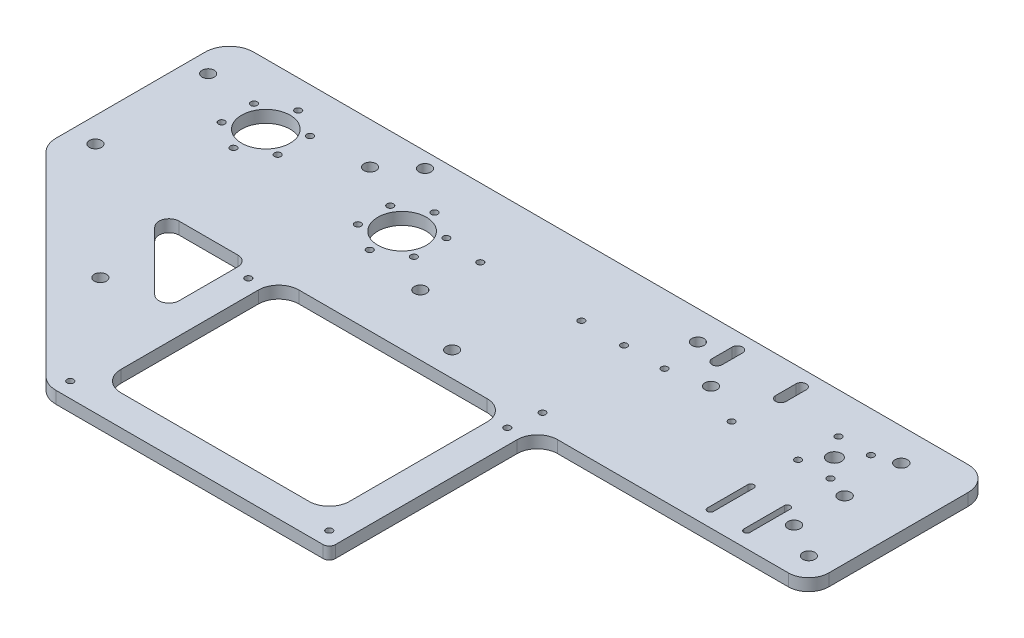
SolidWorks part; units mm, degrees
material "Policarbonato"
ref_plane "Plano frontal" through (0, 0, 0) normal (0, 0, 1) x (1, 0, 0)
ref_plane "Plano superior" through (0, 0, 0) normal (0, 1, 0) x (1, 0, 0)
ref_plane "Plano direito" through (0, 0, 0) normal (1, 0, 0) x (0, 0, -1)
sketch "Esboço1" plane through (0, 0, 0) normal (0, 1, 0) x (1, 0, 0)
  line L3 (-80.5574, -153.6487) -> (51.4721, -153.6487)
  line L4 (54.4721, -150.6487) -> (54.4721, -60.7886)
  line L6 (188.5279, -40.7886) -> (188.5279, 28)
  line L7 (176.5279, 40) -> (-176.5279, 40)
  line L8 (-188.5279, 28) -> (-188.5279, -45.6781)
  line L12 (-122.5768, -50.7886) -> (-93.5279, -50.7886)
  line L13 (-88.5279, -55.7886) -> (-88.5279, -84.8375)
  line L14 (-97.0635, -88.373) -> (-126.1124, -59.3241)
  line L15 (39.4721, -60.6487) -> (39.4721, -128.6487)
  line L16 (29.4721, -138.6487) -> (-63.5279, -138.6487)
  line L17 (-73.5279, -128.6487) -> (-73.5279, -60.6487)
  line L18 (-63.5279, -50.6487) -> (29.4721, -50.6487)
  line L20 (132.5279, 0) -> (148.5279, 0) construction
  line L21 (132.5279, 0) -> (132.5279, 20) construction
  line L22 (132.5279, 20) -> (148.5279, 20) construction
  line L23 (148.5279, 0) -> (148.5279, 20) construction
  line L24 (132.5279, 0) -> (148.5279, 20) construction
  line L25 (132.5279, 20) -> (148.5279, 0) construction
  line L30 (64.4721, -50.7886) -> (178.5279, -50.7886)
  line L31 (150.2221, -43) -> (150.2221, -23) construction
  line L32 (148.7221, -43) -> (148.7221, -23)
  line L33 (151.7221, -43) -> (151.7221, -23)
  line L34 (141.2221, -45.2211) -> (141.2221, -21.4375) construction
  line L36 (132.2221, -43) -> (132.2221, -23) construction
  line L37 (133.7221, -43) -> (133.7221, -23)
  line L38 (130.7221, -43) -> (130.7221, -23)
  line L39 (49.2221, -43) -> (150.2221, -43) construction
  line L40 (54.4721, -120.5) -> (144.9721, -120.5) construction
  line L41 (54.4721, -120.5) -> (54.4721, -7) construction
  line L42 (54.4721, -7) -> (144.9721, -7) construction
  line L43 (144.9721, -120.5) -> (144.9721, -7) construction
  line L44 (54.4721, -120.5) -> (144.9721, -7) construction
  line L45 (54.4721, -7) -> (144.9721, -120.5) construction
  line L46 (70.5279, 22) -> (70.5279, 32) construction
  line L47 (67.9779, 22) -> (67.9779, 32)
  line L48 (73.0779, 22) -> (73.0779, 32)
  line L49 (102.0279, 22) -> (102.0279, 32) construction
  line L50 (99.4779, 22) -> (99.4779, 32)
  line L51 (104.5779, 22) -> (104.5779, 32)
  line L52 (-185.0132, -54.1634) -> (-89.0426, -150.134)
  circle A0 centre (-81.0279, -58.1487) radius 1.6
  circle A1 centre (-81.0279, -146.1487) radius 1.6
  circle A2 centre (46.9721, -58.1487) radius 1.6
  circle A3 centre (46.9721, -146.1487) radius 1.6
  circle A8 centre (176.311, -38.4318) radius 3
  circle A9 centre (0, -38.4318) radius 3
  circle A11 centre (-140.5279, 10) radius 12
  circle A20 centre (-140.5279, 10) radius 16 construction
  circle A21 centre (-140.5279, -6) radius 1.6
  circle A22 centre (-154.3843, 2) radius 1.6
  circle A23 centre (-154.3843, 18) radius 1.6
  circle A24 centre (-84.3674, 32.5) radius 3
  circle A25 centre (-176.311, -38.4318) radius 3
  circle A26 centre (140.5279, 10) radius 3.5
  circle A27 centre (148.5279, 0) radius 1.6
  circle A28 centre (148.5279, 20) radius 1.6
  circle A29 centre (132.5279, 0) radius 1.6
  circle A30 centre (132.5279, 20) radius 1.6
  arc A31 (51.4721, -153.6487) -> (54.4721, -150.6487) centre (51.4721, -150.6487) ccw
  arc A34 (188.5279, 28) -> (176.5279, 40) centre (176.5279, 28) ccw
  arc A35 (-176.5279, 40) -> (-188.5279, 28) centre (-176.5279, 28) ccw
  arc A39 (-93.5279, -50.7886) -> (-88.5279, -55.7886) centre (-93.5279, -55.7886) cw
  arc A40 (-88.5279, -84.8375) -> (-97.0635, -88.373) centre (-93.5279, -84.8375) cw
  arc A41 (-126.1124, -59.3241) -> (-122.5768, -50.7886) centre (-122.5768, -55.7886) cw
  arc A42 (39.4721, -128.6487) -> (29.4721, -138.6487) centre (29.4721, -128.6487) cw
  arc A43 (-63.5279, -138.6487) -> (-73.5279, -128.6487) centre (-63.5279, -128.6487) cw
  arc A44 (-73.5279, -60.6487) -> (-63.5279, -50.6487) centre (-63.5279, -60.6487) cw
  arc A45 (29.4721, -50.6487) -> (39.4721, -60.6487) centre (29.4721, -60.6487) cw
  circle A46 centre (-140.5279, 26) radius 1.6
  circle A47 centre (-126.6715, 18) radius 1.6
  circle A48 centre (-126.6715, 2) radius 1.6
  circle A49 centre (-63.1716, 0) radius 16 construction
  circle A50 centre (-63.1716, -16) radius 1.6
  circle A51 centre (-77.028, -8) radius 1.6
  circle A52 centre (-77.028, 8) radius 1.6
  circle A53 centre (-63.1716, 16) radius 1.6
  circle A54 centre (-49.3152, 8) radius 1.6
  circle A55 centre (-49.3152, -8) radius 1.6
  circle A56 centre (-63.1716, 0) radius 12
  circle A57 centre (-33.5279, -20.6487) radius 3
  circle A58 centre (79.5279, 10) radius 3
  arc A62 (188.5279, -40.7886) -> (178.5279, -50.7886) centre (178.5279, -40.7886) cw
  arc A63 (54.4721, -60.7886) -> (64.4721, -50.7886) centre (64.4721, -60.7886) cw
  arc A64 (148.7221, -43) -> (151.7221, -43) centre (150.2221, -43) ccw
  arc A65 (151.7221, -23) -> (148.7221, -23) centre (150.2221, -23) ccw
  arc A66 (133.7221, -43) -> (130.7221, -43) centre (132.2221, -43) cw
  arc A67 (130.7221, -23) -> (133.7221, -23) centre (132.2221, -23) cw
  circle A68 centre (99.7221, 0) radius 1.6
  circle A69 centre (49.2221, -43) radius 1.6
  circle A70 centre (150.2221, -43) radius 1.6 construction
  circle A71 centre (-30.5279, 6) radius 1.6
  circle A72 centre (19.4721, 6) radius 1.6
  circle A73 centre (60.5279, 6) radius 1.6
  circle A75 centre (40.5279, 6) radius 1.6
  circle A76 centre (70.5279, 27) radius 2.55 construction
  circle A77 centre (102.0279, 27) radius 2.55 construction
  circle A78 centre (159.4679, 24.07) radius 3.05
  circle A79 centre (159.4679, -3.93) radius 3.05
  circle A80 centre (159.4679, -28.93) radius 3.05
  arc A81 (67.9779, 22) -> (73.0779, 22) centre (70.5279, 22) ccw
  arc A82 (73.0779, 32) -> (67.9779, 32) centre (70.5279, 32) ccw
  arc A83 (99.4779, 22) -> (104.5779, 22) centre (102.0279, 22) ccw
  arc A84 (104.5779, 32) -> (99.4779, 32) centre (102.0279, 32) ccw
  circle A85 centre (-178.5279, 19.5) radius 3
  circle A86 centre (-98.5279, 19.5) radius 3
  arc A87 (-80.5574, -153.6487) -> (-89.0426, -150.134) centre (-80.5574, -141.6487) cw
  arc A88 (-185.0132, -54.1634) -> (-188.5279, -45.6781) centre (-176.5279, -45.6781) cw
  circle A89 centre (57.3279, 25.68) radius 3
  point P14 (150.2221, -33)
  point P43 (-140.5279, 10)
  point P70 (-144.4721, -50.6487)
  point P82 (-85.5279, -153.6487)
  point P116 (-63.1716, 0)
  point P123 (0, 40)
  point P124 (132.2221, -33)
  point P129 (99.7221, -63.75)
  point P135 (99.7221, -7)
  point P141 (99.7221, -43)
  point P161 (70.5279, 27)
  point P168 (102.0279, 27)
  dimension "D2" = 3
  dimension "D8" = 12
  dimension "D10" = 12
  dimension "D11" = 61
  dimension "D12" = 203.9448
  dimension "D13" = 7.5
  dimension "D14" = 104.1605
  dimension "D16" = 135.7229
  dimension "D20" = 19.68
  dimension "D21" = 3.2
  dimension "D22" = 48.4318
  dimension "D23" = 32
  dimension "D24" = 3.2
  dimension "D25" = 6
  dimension "D26" = 24
  dimension "D27" = 48
  dimension "D28" = 30
  dimension "D29" = 40
  dimension "D30" = 6
  dimension "D34" = 30
  dimension "D31" = 32
  dimension "D32" = 3.2
  dimension "D33" = 24
  dimension "D35" = 6
  dimension "D36" = 155
  dimension "D37" = 30
  dimension "D44" = 7
  dimension "D48" = 10
  dimension "D6" = 10
  dimension "D58" = 5
  dimension "D62" = 1.5
  dimension "D68" = 101
  dimension "D72" = 80
  dimension "D75" = 5.1
  dimension "D80" = 14.07
  dimension "D82" = 6.1
  dimension "D83" = 10
  dimension "D19" = 6
  dimension "D1" = 137
  dimension "D9" = 377.0558
  dimension "D15" = 225
  dimension "D17" = 38
  dimension "D18" = 15
  dimension "D38" = 48
  dimension "D39" = 15
  dimension "D40" = 12.2169
  dimension "D41" = 12.2169
  dimension "D42" = 16
  dimension "D43" = 20
  dimension "D45" = 15
  dimension "D46" = 15
  dimension "D49" = 7.5
  dimension "D50" = 7.5
  dimension "D51" = 88
  dimension "D52" = 128
  dimension "D53" = 93
  dimension "D56" = 20.6487
  dimension "D57" = 68
  dimension "D59" = 10
  dimension "D60" = 20.5
  dimension "D61" = 20
  dimension "D63" = 9
  dimension "D64" = 113.5
  dimension "D65" = 90.5
  dimension "D66" = 7
  dimension "D67" = 43
  dimension "D69" = 34
  dimension "D70" = 110
  dimension "D71" = 50
  dimension "D73" = 20
  dimension "D74" = 31.5
  dimension "D76" = 13
  dimension "D77" = 10
  dimension "D78" = 25
  dimension "D79" = 28
  dimension "D81" = 18.94
  dimension "D84" = 80
extrude "Ressalto-extrusão1" add sketch "Esboço1" against normal blind 6
sketch "Esboço2" plane through (0, 0, 0) normal (0, 1, 0) x (1, 0, 0)
  line L1 (-126.1124, -59.3241) -> (-97.0635, -88.373) construction
  line L2 (-131.2731, -107.9035) -> (-104.403, -81.0335) construction
  line L3 (-185.0132, -54.1634) -> (-89.0426, -150.134) construction
  circle A1 centre (-117.8381, -94.4685) radius 3
  arc A2 (-188.5279, -45.6781) -> (-185.0132, -54.1634) centre (-176.5279, -45.6781) ccw construction
  point P1 (-117.8381, -94.4685)
  dimension "D1" = 76
  dimension "D2" = 6
extrude "Corte-extrusão1" cut sketch "Esboço2" against normal blind 10
